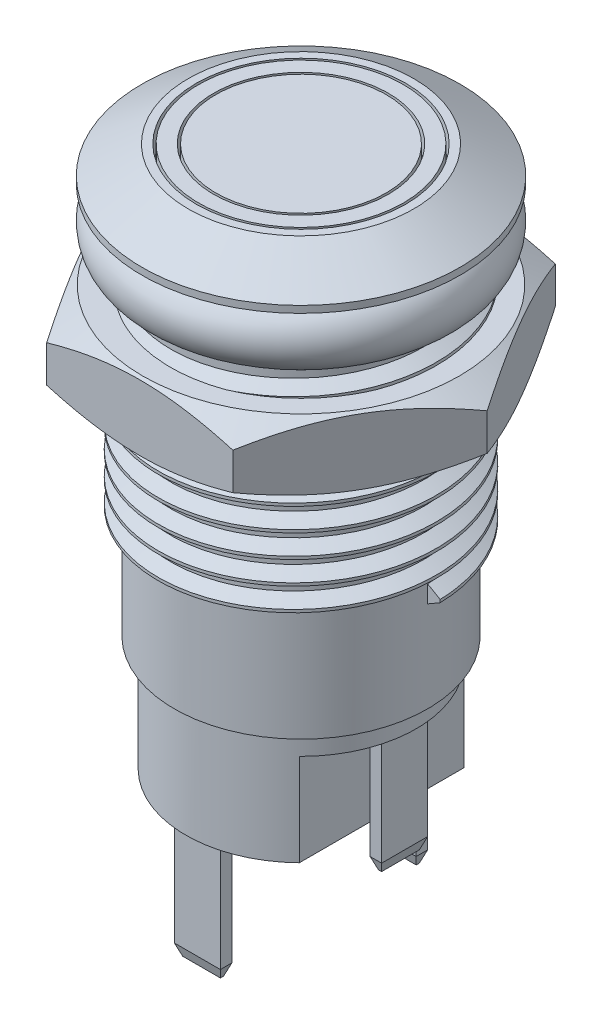
SolidWorks part; units mm, degrees
ref_plane "Спереди" through (0, 0, 0) normal (0, 0, 1) x (1, 0, 0)
ref_plane "Сверху" through (0, 0, 0) normal (0, 1, 0) x (1, 0, 0)
ref_plane "Справа" through (0, 0, 0) normal (1, 0, 0) x (0, 0, -1)
sketch "Эскиз1" plane through (0, 0, 0) normal (0, 0, 1) x (1, 0, 0)
  line L0 (0, 0) -> (0, 23.5) construction
  line L1 (0, 23.5) -> (4.9, 23.5)
  line L2 (4.9, 23.5) -> (6.9, 22.3)
  line L3 (6.9, 22.3) -> (6.9, 22)
  line L5 (5.5, 19.2) -> (5.5, 5)
  line L6 (5.5, 5) -> (5, 5)
  line L7 (5, 5) -> (5, 0)
  line L8 (5, 0) -> (0, 0)
  line L9 (6.9, 22) -> (5.5, 22)
  line L10 (0, 0) -> (0, 23.5)
  line L11 (0, 23.5) -> (0, 0) construction
  arc A1 (5.5, 22) -> (5.5, 19.2) centre (5.5, 20.6) cw
  dimension "D1" = 9.8
  dimension "D2" = 1.5
  dimension "D5" = 11
  dimension "D3" = 13.8
  dimension "D4" = 0.3
  dimension "D6" = 5
  dimension "D7" = 23.5
  dimension "D8" = 10
revolve "Повернуть1" add sketch "Эскиз1" angle 360 about L10
sketch "Эскиз2" plane through (0, 0, 0) normal (0, 0, 1) x (1, 0, 0)
  line L1 (3.5, 4) -> (5, 4)
  line L2 (3.5, 4) -> (3.5, 0)
  line L3 (3.5, 0) -> (5, 0)
  line L4 (5, 4) -> (5, 0)
  line L5 (3.5, 4) -> (5, 0) construction
  line L6 (3.5, 0) -> (5, 4) construction
  line L7 (-5, 0) -> (5, 0) construction
  line L8 (-5, 4) -> (-3.5, 4)
  line L9 (-5, 4) -> (-5, 0)
  line L10 (-5, 0) -> (-3.5, 0)
  line L11 (-3.5, 4) -> (-3.5, 0)
  line L12 (-5, 4) -> (-3.5, 0) construction
  line L13 (-5, 0) -> (-3.5, 4) construction
  line L14 (-5, 5) -> (-5, 0) construction
  line L15 (5, 0) -> (5, 5) construction
  point P4 (4.25, 2)
  point P12 (-4.25, 2)
  dimension "D1" = 7
  dimension "D2" = 4
extrude "Вырез-Вытянуть1" cut sketch "Эскиз2" against normal through all both and the other way through all
thread "Резьба1" pitch 1 method extrude profile "Профиль резьбы1" start angle 0, offset 0, length 9.5, pitch 1, diameter 11
ref_plane "Плоскость1" through (-5.5, 19.2, 0) normal (0, 0, 1) x (-1, 0, 0)
sketch "Профиль резьбы1" plane through (-5.5, 19.2, 0) normal (0, 0, 1) x (-1, 0, 0)
  line L0 (0, 0) -> (0, 1) construction
  line L1 (0, 0) -> (0.5413, 0.3125)
  line L2 (0.5413, 0.3125) -> (0.5413, 0.4375)
  line L3 (0.5413, 0.4375) -> (0, 0.75)
  line L4 (0.5413, 0.375) -> (0, 0.375) construction
  line L11 (0, 0) -> (0, 0.75)
  point P2 (0, 0)
  dimension "Pitch" = 1
  dimension "Profile_Angle" = 60
  dimension "Profile_Land" = 0.125
  dimension "Profile_Height" = 0.5413
sketch "Эскиз5" plane through (0, 4, 0) normal (0, -1, 0) x (1, 0, 0)
  line L0 (3.5, -3.5707) -> (3.5, 3.5707) construction
  line L1 (4, 1) -> (4.5, 1)
  line L2 (4, 1) -> (4, -1)
  line L3 (4, -1) -> (4.5, -1)
  line L4 (4.5, 1) -> (4.5, -1)
  line L5 (4, 1) -> (4.5, -1) construction
  line L6 (4, -1) -> (4.5, 1) construction
  circle A0 centre (0, 0) radius 4.25 construction
  point P4 (4.25, 0)
  dimension "D1" = 0.5
  dimension "D2" = 2
  dimension "D3" = 0.5
extrude "Бобышка-Вытянуть1" add sketch "Эскиз5" along normal blind 5.3
chamfer "Фаска1" distance 0.5 angle 20 4 edges at (4.25, -1.3, 1) (4, -1.3, 0) (4.25, -1.3, -1) (4.5, -1.3, 0) first distance on face at (4.25, 1.35, 1) first distance on face at (4, 1.35, 0) first distance on face at (4.25, 1.35, -1) first distance on face at (4.5, 1.35, 0)
pattern_circular "Круговой массив1" count 2 over 360 about axis through (0, 0, 0) along (0, -1, 0) of "Фаска1", "Бобышка-Вытянуть1"
ref_plane "Плоскость2" through (0, 18.2, 0) normal (0, 1, 0) x (1, 0, 0)
sketch "Эскиз6" plane through (0, 18.2, 0) normal (0, 1, 0) x (1, 0, 0)
  line L1 (8.0829, 0) -> (4.0415, 7)
  line L2 (4.0415, 7) -> (-4.0415, 7)
  line L3 (-4.0415, 7) -> (-8.0829, 0)
  line L4 (-8.0829, 0) -> (-4.0415, -7)
  line L5 (-4.0415, -7) -> (4.0415, -7)
  line L6 (4.0415, -7) -> (8.0829, 0)
  circle A0 centre (0, 0) radius 7 construction
  dimension "D1" = 14
extrude "Бобышка-Вытянуть2" add sketch "Эскиз6" against normal blind 3
sketch "Эскиз7" plane through (0, 0, 0) normal (0, 0, 1) x (1, 0, 0)
  line L0 (-8.0829, 18.2) -> (-8.0829, 17.5)
  line L2 (-8.0829, 17.5) -> (-6.8705, 18.2)
  line L3 (4.0415, 18.2) -> (8.0829, 18.2) construction
  line L4 (-6.8705, 18.2) -> (-8.0829, 18.2)
  line L5 (-8.0829, 15.9) -> (-8.0829, 15.2)
  line L6 (-8.0829, 15.2) -> (-6.8705, 15.2)
  line L7 (4.0415, 15.2) -> (8.0829, 15.2) construction
  line L9 (-8.0829, 15.2) -> (-4.0415, 15.2) construction
  line L10 (-8.0829, 15.9) -> (-6.8705, 15.2)
  line L11 (-8.0829, 15.2) -> (-8.0829, 18.2) construction
  point P3 (-8.0829, 17.5)
  dimension "D1" = 30
  dimension "D2" = 0.7
revolve "Вырез-Повернуть1" cut sketch "Эскиз7" angle 360 about L10 region at (-7.6788, 17.9667, 0) region at (-7.6788, 15.4333, 0)
sketch "Эскиз8" plane through (0, 0, 0) normal (0, -1, 0) x (1, 0, 0)
  line L0 (4, 1) -> (4.5, 1) construction
  line L1 (-1, 4.5) -> (1, 4.5)
  line L2 (-1, 4.5) -> (-1, 4)
  line L3 (-1, 4) -> (1, 4)
  line L4 (1, 4.5) -> (1, 4)
  line L5 (-1, 4.5) -> (1, 4) construction
  line L6 (-1, 4) -> (1, 4.5) construction
  line L7 (4, 1) -> (4, -1) construction
  circle A0 centre (0, 0) radius 4.25 construction
  point P4 (0, 4.25)
extrude "Бобышка-Вытянуть3" add sketch "Эскиз8" along normal blind 5.3
chamfer "Фаска2" distance 0.5 angle 20 4 edges at (-1, -5.3, 4.25) (0, -5.3, 4) (1, -5.3, 4.25) (0, -5.3, 4.5) first distance on face at (-1, -2.65, 4.25) first distance on face at (0, -2.65, 4) first distance on face at (1, -2.65, 4.25) first distance on face at (0, -2.65, 4.5)
pattern_circular "Круговой массив2" count 2 over 360 about axis through (0, 0, 0) along (0, -1, 0) of "Бобышка-Вытянуть3", "Фаска2" reverse direction yes
sketch "Эскиз9" plane through (0, 23.5, 0) normal (0, 1, 0) x (1, 0, 0)
  circle A0 centre (0, 0) radius 4.5
  circle A1 centre (0, 0) radius 3.75
  dimension "D1" = 9
  dimension "D2" = 7.5
extrude "Вырез-Вытянуть-Тонкостенный1" cut sketch "Эскиз9" against normal blind 1 thin contours A0 | A1 thin type mid plane wall 0.1
